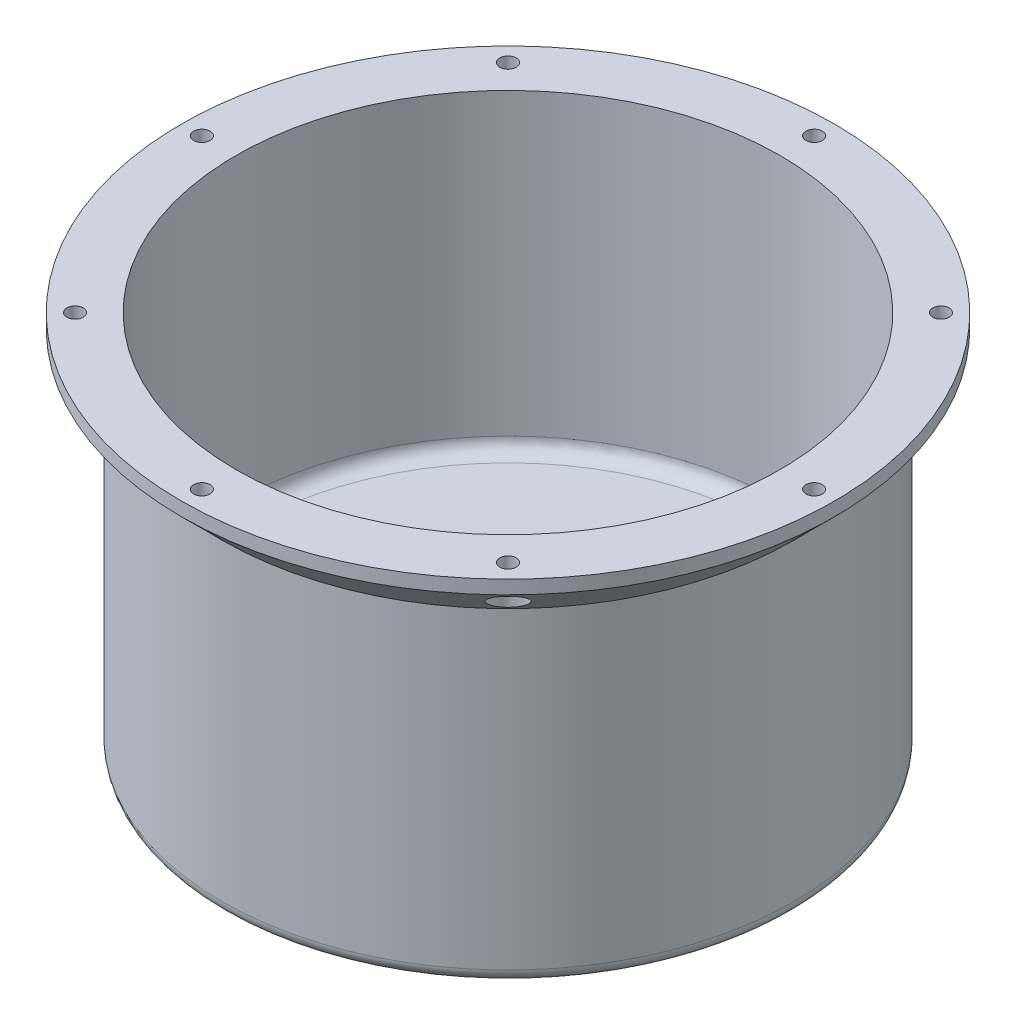
SolidWorks part; units mm, degrees
material "6061-T6 (SS)"
ref_plane "Front Plane" through (0, 0, 0) normal (0, 0, 1) x (1, 0, 0)
ref_plane "Top Plane" through (0, 0, 0) normal (0, 1, 0) x (1, 0, 0)
ref_plane "Right Plane" through (0, 0, 0) normal (1, 0, 0) x (0, 0, -1)
sketch "Sketch1" plane through (0, 0, 0) normal (0, 0, 1) x (1, 0, 0)
  line L0 (0, 0) -> (0, 26.2766) construction
  line L1 (0, 0) -> (-10, 0)
  line L2 (-105, 0) -> (-105, 100)
  line L3 (-105, 100) -> (-120, 115)
  line L4 (-120, 115) -> (-120, 120)
  line L5 (-120, 120) -> (-100, 120)
  line L6 (-100, 120) -> (-100, 5)
  line L7 (-100, 5) -> (0, 5)
  line L8 (0, 5) -> (0, 0)
  line L9 (-10, 0) -> (-10, -20)
  line L10 (-10, -20) -> (-105, -20)
  line L11 (-105, -20) -> (-105, 0)
  point P6 (-110, 120)
  point P14 (-105, -8.0726)
  point P16 (0, 0)
  dimension "D1" = 5
  dimension "D2" = 5
  dimension "D3" = 200
  dimension "D4" = 120
  dimension "D5" = 5
  dimension "D6" = 45
  dimension "D7" = 20
  dimension "D8" = 20
  dimension "D9" = 20
revolve "Revolve1" add sketch "Sketch1" angle 360 about L0
cosmetic thread "Cosmetic Thread1" parameters "D2"=24
sketch "Sketch3" plane through (0, 120, 0) normal (0, 1, 0) x (1, 0, 0)
  circle A0 centre (0, 0) radius 112.5 construction
  circle A1 centre (0, 112.5) radius 3
  circle A2 centre (0, 112.5) radius 6
  dimension "D1" = 225
  dimension "D2" = 6
  dimension "D3" = 12
extrude "Cut-Extrude1" cut sketch "Sketch3" against normal through all and the other way through all contours A1 region at (0, 120, -112.5)
extrude "Cut-Extrude2" cut sketch "Sketch3<3>" against normal through all from offset 5 contours A2 A1 region at (-5.8303, 120, -112.5) offset against normal yes
sketch "Sketch3<3>" plane through (0, 120, 0) normal (0, 1, 0) x (1, 0, 0) same geometry as "Sketch3"
pattern_circular "CirPattern1" count 8 over 360 about axis through (0, 120, 0) along (0, -1, 0) of "Cut-Extrude1", "Cut-Extrude2"
fillet "Fillet2" radius 5 2 edges at (0, 5, -100) (0, -20, -105)
